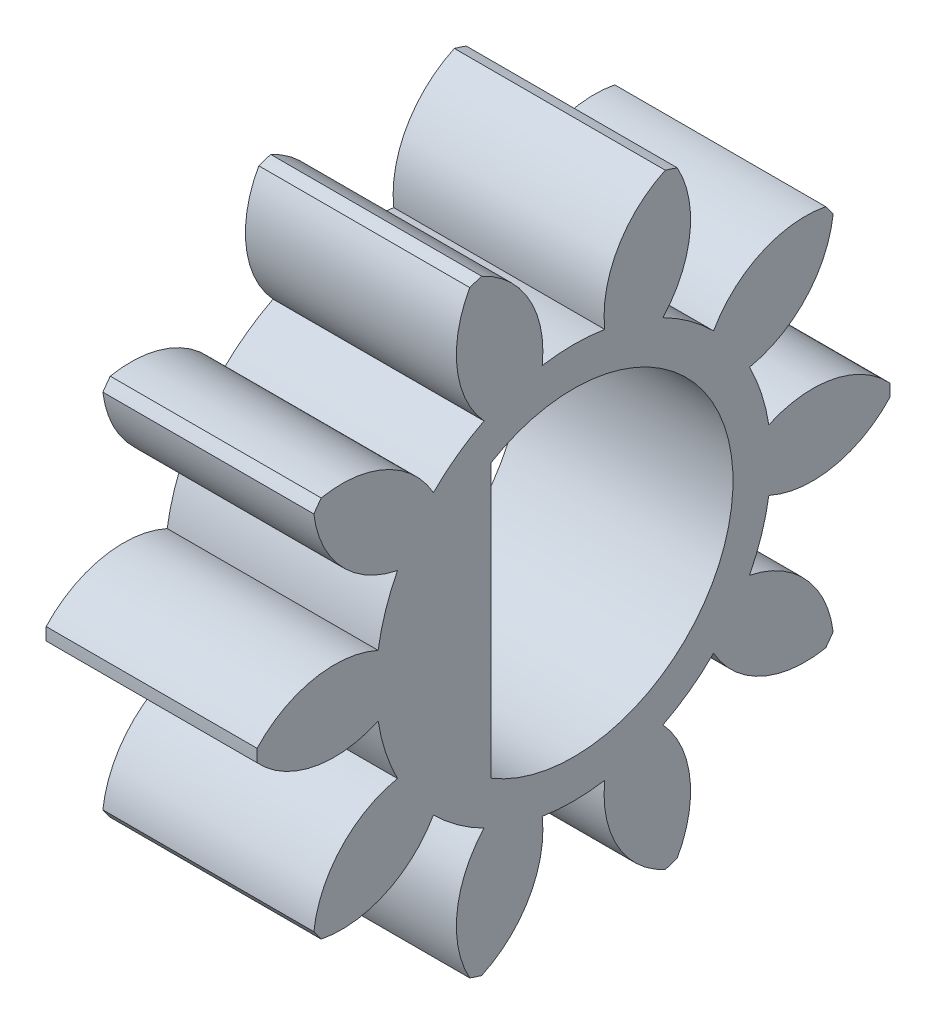
SolidWorks part; units mm, degrees
ref_plane "Plane1" through (0, 0, 0) normal (0, 0, 1) x (1, 0, 0)
ref_plane "Plane2" through (0, 0, 0) normal (0, 1, 0) x (1, 0, 0)
ref_plane "Plane3" through (0, 0, 0) normal (1, 0, 0) x (0, 0, -1)
other "Configuration Table"
sketch "HoldingSke" plane through (0, 0, 0) normal (0, 1, 0) x (1, 0, 0)
  line L0 (0, 0) -> (0.9848, -0.1736)
  line L1 (-15, 0) -> (100, 0) construction
  line L2 (0, 0) -> (-2.1039, 2.3779)
  line L3 (0, 0) -> (-11.863, 4.5341)
  line L4 (0, 0) -> (8.5048, 1.4996)
  line L5 (0, 0) -> (-46.8476, -17.4728)
  line L6 (0, 0) -> (-3.3159, -2.2372)
  line L7 (-2.1039, 2.3779) -> (8.6586, 51.2059)
  line L8 (-76.2, 54.61) -> (-75.2, 54.61)
  line L9 (-71.009, 38.7566) -> (-53.1078, 45.2721)
  line L10 (-76.2, 71.12) -> (104.1128, 71.12)
  line L11 (0, 0) -> (-4, 0)
  line L12 (-76.2, 101.6) -> (-76.162, 101.6)
  line L13 (24.9733, 27.94) -> (52.9518, 28.4284)
  line L14 (24.9733, 27.94) -> (24.9743, 27.94)
  line L15 (24.9733, 27.94) -> (100.4006, 29.5858)
  line L16 (-63.627, -1) -> (-12.827, -1)
  circle A0 centre (0, 0) radius 3
  circle A1 centre (0, 0) radius 3.749
  circle A2 centre (0, 0) radius 37.5
  circle A3 centre (0, 0) radius 3
  dimension "Num_teeth" = 10
  dimension "Pitch_radius" = 180.3128
  dimension "Width" = 4
  dimension "Thickness" = 4
sketch "BasProSke" plane through (0, 0, 0) normal (0, 1, 0) x (1, 0, 0)
  line L0 (-10, 0) -> (60, 0) construction
  line L1 (0, 0) -> (0, 6)
  line L2 (0, 0) -> (4, 0)
  line L3 (4, 0) -> (4, 6)
  line L4 (4, 6) -> (0, 6)
  dimension "Thickness" = 4
  dimension "Diameter" = 12
revolve "Base-Revolve" add sketch "BasProSke" angle 360 about L0
sketch "TooCutSke" plane through (0, 0, 0) normal (1, 0, 0) x (0, 0, -1)
  line L1 (0, 0) -> (0, 107) construction
  line L2 (0, 0) -> (-0.8485, 4.9275) construction
  line L3 (0, 0) -> (-3.0584, 9.4126) construction
  line L4 (-0.8485, 4.9275) -> (-1.5292, 4.7063) construction
  arc A0 (0.5928, 3.7018) -> (-0.5928, 3.7018) centre (0, 0) ccw
  arc A1 (1.7758, 5.7578) -> (-1.7758, 5.7578) centre (0, 0) ccw
  circle A2 centre (0, 0) radius 5 construction
  circle A3 centre (0, 0) radius 4.6985 construction
  arc A4 (-0.5928, 3.7018) -> (-1.7758, 5.7578) centre (-2.5801, 3.9267) ccw
  arc A5 (1.7758, 5.7578) -> (0.5928, 3.7018) centre (2.5801, 3.9267) ccw
extrude "ToothCut" cut sketch "TooCutSke" along normal through all
fillet "Breaks" [suppressed] radius 0.02 tangent propagation no
fillet "RootFillets" [suppressed] radius 0.251
pattern_circular "TeethCuts" count 10 every 36 about axis through (-10, 0, 0) along (1, 0, 0) of "ToothCut", "RootFillets", "Breaks"
sketch "HubNeaOneSke" plane through (0, 0, 0) normal (-1, 0, 0) x (0, 0, 1)
  circle A0 centre (0, 0) radius 3.749
  dimension "Diameter" = 7.498
extrude "HubNearOne" [suppressed] add sketch "HubNeaOneSke" along normal blind 46.0001
sketch "HubNeaBotSke" plane through (0, 0, 0) normal (-1, 0, 0) x (0, 0, 1)
  circle A0 centre (0, 0) radius 3.749
  dimension "Diameter" = 7.498
extrude "HubNearBoth" [suppressed] add sketch "HubNeaBotSke" along normal blind 23
ref_plane "FarPln" through (4, 0, 0) normal (1, 0, 0) x (0, 0, -1)
sketch "HubFarSke" plane through (4, 0, 0) normal (1, 0, 0) x (0, 0, -1)
  circle A0 centre (0, 0) radius 3.749
  dimension "Diameter" = 7.498
extrude "HubFar" [suppressed] add sketch "HubFarSke" along normal blind 23
sketch "BorSke" plane through (0, 0, 0) normal (1, 0, 0) x (0, 0, -1)
  circle A0 centre (0, 0) radius 3.025
  dimension "Diameter" = 6.05
extrude "Bore" cut sketch "BorSke" along normal mid plane 100.0001
sketch "KeySke" plane through (0, 0, 0) normal (1, 0, 0) x (0, 0, -1)
  line L0 (-1, 0) -> (-1, 4)
  line L1 (-1, 4) -> (1, 4)
  line L2 (1, 4) -> (1, 0)
  line L3 (0, 0) -> (0, 34) construction
  line L4 (-1, 0) -> (1, 0)
  dimension "Width" = 2
extrude "Keyway" [suppressed] cut sketch "KeySke" along normal mid plane 100.0001
pattern_circular "Keyway2" [suppressed] count 2 every 90 about axis through (-10, 0, 0) along (1, 0, 0)
ref_axis "Axis1" through (4, 0, 0) along (-1, 0, 0)
sketch "Sketch2" plane through (0, 0, 0) normal (-1, 0, 0) x (0, 0, 1)
  circle A0 centre (0, 0) radius 3.025
  dimension "D1" = 6.05
sketch "Sketch1" plane through (0, 0, 0) normal (-1, 0, 0) x (0, 0, 1)
  line L0 (1.565, 2.5887) -> (1.565, -2.5887)
  line L1 (1.565, 0) -> (-3.025, 0) construction
  line L2 (1.565, 0) -> (3.025, 0) construction
  circle A0 centre (0, 0) radius 3.025 construction
  arc A1 (1.565, 2.5887) -> (1.565, -2.5887) centre (0, 0) cw
  circle M2 centre (0, 0) radius 3.025
  dimension "D1" = 1.46
extrude "Boss-Extrude1" add sketch "Sketch1" against normal up to surface (4 mm away) contours L0 M2 region at (0, 0, 2.1631) up to face at (4, 0, 3.025)
equation "' \"Module@HoldingSke\" = 6.35"
equation "' \"Num_teeth@HoldingSke\" = 12"
equation "' \"Ap@HoldingSke\" =  20"
equation "' \"Ap@HoldingSke\" = 20"
equation "' \"Width@HoldingSke\" = 0.5 * 25.4"
equation "' \"Hub_dia@HoldingSke\"= 1 * 25.4"
equation "' \"Hub_dia@HoldingSke\" = 1 * 25.4"
equation "' \"Overall_len@HoldingSke\" = 1.0 * 25.4"
equation "' \"Bore@HoldingSke\" = 0.75 * 25.4"
equation "' \"T_dim@HoldingSke\" = 0.1 * 25.4"
equation "' \"Width@KeySke\" = 0.25 * 25.4"
equation "' \"Show_teeth@HoldingSke\" = 13"
equation "' \"Backlash@HoldingSke\" = 0.009 * 25.4"
equation "' \"Addendum_fac@HoldingSke\" = 1.0"
equation "' \"Dedendum_fac@HoldingSke\" = 1.25"
equation "' \"Dedendum_add@HoldingSke\" = 0.00005 * 25.4"
equation "' \"Clearance_fac@HoldingSke\" = 0.25"
equation "\"Pitch@HoldingSke\" = 1 / \"Module@HoldingSke\""
equation "\"Overcut_dia@TooCutSke\" = (\"Num_teeth@HoldingSke\" + 2 * \"Addendum_fac@HoldingSke\") / \"Pitch@HoldingSke\" + 0.002 * 25.4"
equation "\"Pitch_dia@TooCutSke\" = \"Num_teeth@HoldingSke\" / \"Pitch@HoldingSke\""
equation "\"Base_dia@TooCutSke\" = \"Num_teeth@HoldingSke\" / \"Pitch@HoldingSke\" * cos((\"Ap@HoldingSke\"  * 3.14159265 / 180))"
equation "\"Root_dia@TooCutSke\" = (\"Num_teeth@HoldingSke\" + 2) / \"Pitch@HoldingSke\" - 2 * (\"Addendum_fac@HoldingSke\" + \"Dedendum_fac@HoldingSke\") / \"Pitch@HoldingSke\" - \"Dedendum_add@HoldingSke\" * 2"
equation "\"Half_ang@TooCutSke\" = 180 / \"Num_teeth@HoldingSke\""
equation "\"Half_CT@TooCutSke\" = \"Num_teeth@HoldingSke\" / \"Pitch@HoldingSke\" * sin((3.14159265 / 2 / \"Num_teeth@HoldingSke\")) / 2 - 7 * \"Backlash@HoldingSke\" / 4"
equation "\"Flank_rad@TooCutSke\" = \"Num_teeth@HoldingSke\" / \"Pitch@HoldingSke\" / 5"
equation "\"Radius@RootFillets\" = \"Clearance_fac@HoldingSke\" / \"Pitch@HoldingSke\" + \"Dedendum_add@HoldingSke\""
equation "\"Break_rad@Breaks\" = 0.02 / \"Pitch@HoldingSke\""
equation "\"Thickness@HoldingSke\" = \"Width@HoldingSke\""
equation "\"OAL@HoldingSke\" = \"Thickness@HoldingSke\""
equation "\"MHD@HoldingSke\" = (\"Num_teeth@HoldingSke\" + 2) / \"Pitch@HoldingSke\" - 2 * (\"Addendum_fac@HoldingSke\" + \"Dedendum_fac@HoldingSke\")  / \"Pitch@HoldingSke\" - \"Dedendum_add@HoldingSke\" * 2"
equation "\"MBD@HoldingSke\" = (\"Num_teeth@HoldingSke\" + 2) / \"Pitch@HoldingSke\" - 2 * (\"Addendum_fac@HoldingSke\" + \"Dedendum_fac@HoldingSke\")  / \"Pitch@HoldingSke\" - \"Dedendum_add@HoldingSke\" * 2 - 0.002 * 25.4"
equation "\"MHD@HoldingSke\" = ((sgn( \"MHD@HoldingSke\" - \"Hub_dia@HoldingSke\" )-1)*( \"MHD@HoldingSke\" - \"Hub_dia@HoldingSke\" ))/-2+ \"Hub_dia@HoldingSke\""
equation "\"MBD@HoldingSke\" = ((sgn( \"MBD@HoldingSke\" - \"Bore@HoldingSke\" )-1)*( \"MBD@HoldingSke\" - \"Bore@HoldingSke\" ))/-2+ \"Bore@HoldingSke\""
equation "\"OAL@HoldingSke\" = ((sgn( \"OAL@HoldingSke\" - \"Overall_len@HoldingSke\" )+1)*( \"OAL@HoldingSke\" - \"Overall_len@HoldingSke\" ))/2 + \"Overall_len@HoldingSke\" + 0.000002 * 25.4"
equation "\"Num_teeth@TeethCuts\" = int( \"Show_teeth@HoldingSke\" ) + 1"
equation "\"Num_teeth@TeethCuts\" = ((sgn( \"Num_teeth@TeethCuts\" - \"Num_teeth@HoldingSke\" )-1)*( \"Num_teeth@TeethCuts\" - \"Num_teeth@HoldingSke\" ))/-2+ \"Num_teeth@HoldingSke\""
equation "\"Num_teeth@TeethCuts\" = ((sgn( \"Num_teeth@TeethCuts\" - 2.0)+1)*( \"Num_teeth@TeethCuts\" - 2.0))/2 +2.0"
equation "\"Angle@TeethCuts\" = 360.0 / \"Num_teeth@HoldingSke\""
equation "\"Diameter@BasProSke\" = (\"Num_teeth@HoldingSke\" + 2 * \"Addendum_fac@HoldingSke\") / \"Pitch@HoldingSke\""
equation "\"Thickness@BasProSke\"  = \"Thickness@HoldingSke\""
equation "' \"Fillet_rad@BasProSke\" =  \"Thickness@HoldingSke\" * 0.05"
equation "' \"Fillet_rad@BasProSke\" = \"Thickness@HoldingSke\" * 0.05"
equation "\"MHD@HoldingSke\" = ((sgn( \"MHD@HoldingSke\" - \"Root_dia@TooCutSke\" )-1)*( \"MHD@HoldingSke\" - \"Root_dia@TooCutSke\" ))/-2+ \"Root_dia@TooCutSke\""
equation "\"Diameter@HubNeaOneSke\" = \"MHD@HoldingSke\""
equation "\"Length@HubNearOne\" = \"OAL@HoldingSke\" - \"Thickness@BasProSke\""
equation "\"Diameter@HubNeaBotSke\" = \"MHD@HoldingSke\""
equation "\"Length@HubNearBoth\" = ( \"OAL@HoldingSke\" - \"Thickness@BasProSke\" ) / 2.0"
equation "\"Thickness@FarPln\" = \"Thickness@BasProSke\""
equation "\"Diameter@HubFarSke\" = \"MHD@HoldingSke\""
equation "\"Length@HubFar\" = ( \"OAL@HoldingSke\" - \"Thickness@BasProSke\" ) / 2.0"
equation "\"Diameter@BorSke\"=6.05"
equation "\"D1@Bore\" = \"OAL@HoldingSke\" * 2.0"
equation "\"D1@Keyway\" = \"OAL@HoldingSke\" * 2.0"
equation "\"Offset@KeySke\" = \"T_dim@HoldingSke\" + \"MBD@HoldingSke\" / 2.0"
